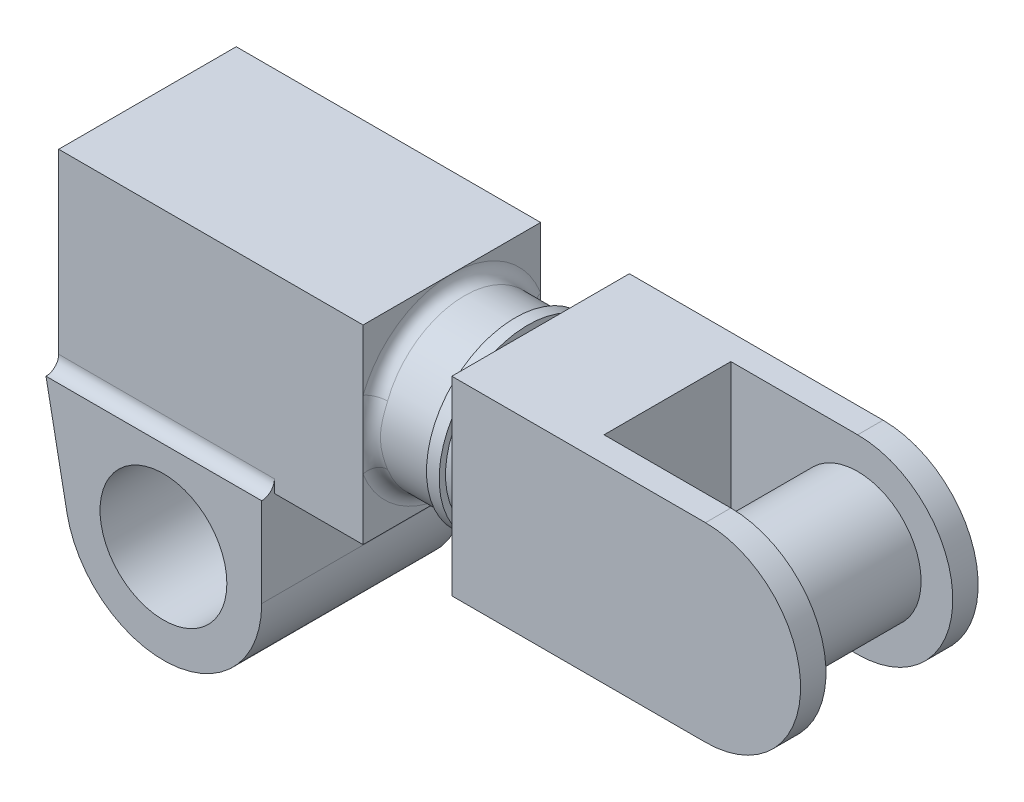
SolidWorks part; units mm, degrees
ref_plane "Front Plane" through (0, 0, 0) normal (0, 0, 1) x (1, 0, 0)
ref_plane "Top Plane" through (0, 0, 0) normal (0, 1, 0) x (1, 0, 0)
ref_plane "Right Plane" through (0, 0, 0) normal (1, 0, 0) x (0, 0, -1)
sketch "Sketch1" plane through (0, 0, 0) normal (1, 0, 0) x (0, 0, -1)
  line L1 (-70, -75) -> (70, -75)
  line L2 (-70, -75) -> (-70, 75)
  line L3 (-70, 75) -> (70, 75)
  line L4 (70, -75) -> (70, 75)
  line L5 (-70, -75) -> (70, 75) construction
  line L6 (-70, 75) -> (70, -75) construction
  point P0 (0, 0)
  dimension "D1" = 150
  dimension "D2" = 140
extrude "Boss-Extrude1" add sketch "Sketch1" along normal blind 240
sketch "Sketch2" plane through (240, 0, 0) normal (1, 0, 0) x (0, 0, -1)
  circle A0 centre (0, 0) radius 65
  dimension "D1" = 130
extrude "Boss-Extrude2" add sketch "Sketch2" along normal blind 50
sketch "Sketch3" plane through (290, 0, 0) normal (1, 0, 0) x (0, 0, -1)
  circle A0 centre (0, 0) radius 70
  dimension "D1" = 140
extrude "Boss-Extrude3" add sketch "Sketch3" along normal blind 10
sketch "Sketch4" plane through (0, 0, 0) normal (0, 0, 1) x (1, 0, 0)
  line L0 (0, -75) -> (16.5223, -160)
  line L1 (0, 75) -> (0, -75) construction
  line L2 (170.0984, -145.2123) -> (170.0984, -75)
  line L5 (240, -75) -> (0, -75) construction
  line L6 (0, -75) -> (170.0984, -75)
  arc A0 (16.5223, -160) -> (170.0984, -145.2123) centre (92.5984, -145.2123) ccw
  circle A1 centre (92.5984, -145.2123) radius 50
  dimension "D1" = 155
  dimension "D2" = 100
  dimension "D3" = 191
  dimension "D4" = 85
extrude "Boss-Extrude4" add sketch "Sketch4" along normal mid plane 160
fillet "Fillet1" radius 10 3 edges at (240, 0, -65) (85.0492, -75, 70) (85.0492, -75, -70)
sketch "Sketch5" plane through (300, 0, 0) normal (1, 0, 0) x (0, 0, -1)
  circle A0 centre (0, 0) radius 65
  dimension "D1" = 130
extrude "Boss-Extrude5" add sketch "Sketch5" along normal mid plane 20
sketch "Sketch6" plane through (0, 0, 0) normal (0, 0, 1) x (1, 0, 0)
  line L0 (510, 75) -> (310, 75)
  line L1 (310, 75) -> (310, -75)
  line L2 (310, -75) -> (510, -75)
  line L3 (310, -65) -> (310, 65) construction
  arc A0 (510, -75) -> (510, 75) centre (510, 0) ccw
  dimension "D1" = 150
  dimension "D2" = 200
extrude "Boss-Extrude6" add sketch "Sketch6" along normal mid plane 140
sketch "Sketch7" plane through (0, 0, 0) normal (0, 0, 1) x (1, 0, 0)
  line L0 (510, 75) -> (410, 75)
  line L1 (510, 75) -> (310, 75) construction
  line L2 (410, 75) -> (410, -75)
  line L3 (310, -75) -> (510, -75) construction
  line L4 (410, -75) -> (510, -75)
  arc A0 (510, -75) -> (510, 75) centre (510, 0) ccw construction
  arc A1 (510, -75) -> (510, 75) centre (510, 0) ccw
extrude "Cut-Extrude1" cut sketch "Sketch7" against normal mid plane 100
sketch "Sketch10" plane through (0, 0, -50) normal (0, 0, 1) x (1, 0, 0)
  circle A0 centre (510, 0) radius 50
  dimension "D1" = 100
extrude "Boss-Extrude7" add sketch "Sketch10" along normal blind 100
sketch "Sketch11" plane through (0, 0, -70) normal (0, 0, -1) x (-1, 0, 0)
  text T0 "ABB" font "Broadway" height in points 146
extrude "Boss-Extrude8" add sketch "Sketch11" along normal blind 15
